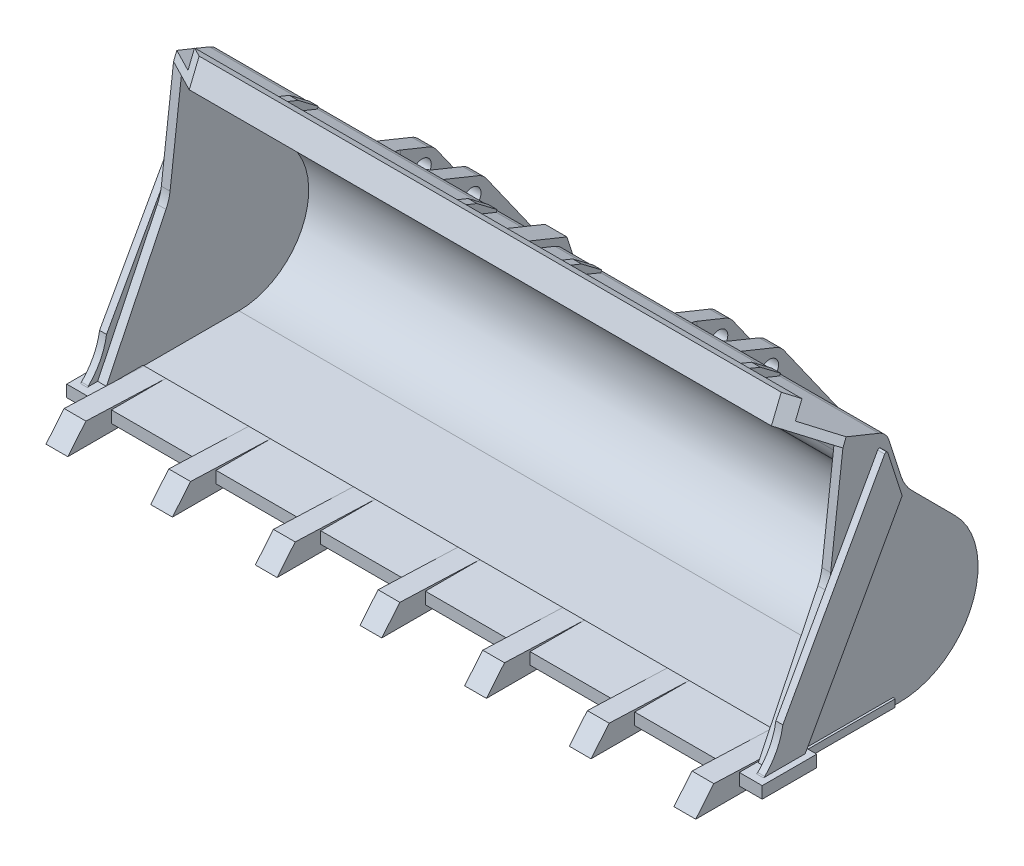
SolidWorks part; units mm, degrees
ref_plane "Front Plane" through (0, 0, 0) normal (0, 0, 1) x (1, 0, 0)
ref_plane "Top Plane" through (0, 0, 0) normal (0, 1, 0) x (1, 0, 0)
ref_plane "Right Plane" through (0, 0, 0) normal (1, 0, 0) x (0, 0, -1)
sketch "Sketch1" plane through (0, 0, 0) normal (1, 0, 0) x (0, 0, -1)
  line L0 (76.25, 0) -> (0, 0)
  line L1 (0, 0) -> (0, 5)
  line L2 (0, 5) -> (36.25, 80)
  line L3 (36.25, 80) -> (43.75, 142.5)
  line L4 (43.75, 142.5) -> (27.7663, 148.9871)
  line L5 (27.7663, 148.9871) -> (33.4072, 162.886)
  line L6 (33.4072, 162.886) -> (38.0402, 161.0057)
  line L7 (38.0402, 161.0057) -> (34.2795, 151.7398)
  line L8 (34.2795, 151.7398) -> (68.7006, 137.7697)
  line L9 (68.7006, 137.7697) -> (78.9617, 106.0197)
  line L10 (78.9617, 106.0197) -> (108.1198, 76.7697)
  arc A0 (108.1198, 76.7697) -> (76.25, 0) centre (76.25, 45) cw
  dimension "D15" = 45
  dimension "D1" = 5
  dimension "D2" = 80
  dimension "D3" = 36.25
  dimension "D4" = 142.5
  dimension "D5" = 43.75
  dimension "D6" = 76.25
  dimension "D7" = 17.25
  dimension "D8" = 10
  dimension "D9" = 5
  dimension "D10" = 5
  dimension "D11" = 130
  dimension "D12" = 153
  dimension "D13" = 31.75
  dimension "D14" = 29.25
extrude "Boss-Extrude1" add sketch "Sketch1" against normal blind 191.875
fillet "Fillet1" radius 25 1 edges at (-95.9375, 106.0197, -78.9617)
fillet "Fillet2" radius 10 1 edges at (-95.9375, 137.7697, -68.7006)
fillet "Fillet3" radius 25 1 edges at (-95.9375, 80, -36.25)
shell "Shell1" thickness 5 removed face at (-191.875, 99.0116, -50.2449) removed face at (-95.9375, 2.5, 0) removed face at (-95.9375, 40.6214, -17.217) removed face at (-95.9375, 80.1451, -35.7543) removed face at (-95.9375, 113.3217, -40.2486)
sketch "Sketch3" plane through (-191.875, 0, 0) normal (-1, 0, 0) x (0, 0, 1)
  line L0 (0, 5) -> (0, 0) construction
  line L1 (-21.25, 5.5) -> (10, 5.5)
  line L2 (-21.25, 5.5) -> (-21.25, -1.25)
  line L3 (-21.25, -1.25) -> (10, -1.25)
  line L4 (10, 5.5) -> (10, -1.25)
  line L5 (0, 0) -> (-76.25, 0) construction
  dimension "D1" = 31.25
  dimension "D2" = 6.75
  dimension "D3" = 10
  dimension "D4" = 1.25
extrude "Boss-Extrude3" add sketch "Sketch3" against normal blind 199.375
sketch "Sketch4" plane through (-191.875, 0, 0) normal (-1, 0, 0) x (0, 0, 1)
  line L1 (-21.25, 0) -> (-72.5, 0)
  line L2 (-21.25, 0) -> (-21.25, 4.25)
  line L3 (-21.25, 4.25) -> (-72.5, 4.25)
  line L4 (-72.5, 0) -> (-72.5, 4.25)
  dimension "D1" = 51.25
  dimension "D2" = 4.25
extrude "Boss-Extrude4" add sketch "Sketch4" against normal blind 193.125
sketch "Sketch5" plane through (0, 0, 0) normal (1, 0, 0) x (0, 0, -1)
  line L0 (-7, 4) -> (17.2963, 4)
  line L1 (17.2963, 4) -> (73.7585, 105.8605)
  line L2 (73.7585, 105.8605) -> (64.8101, 133.5489)
  line L3 (64.8101, 133.5489) -> (5.3334, 26.25)
  line L4 (77.1159, 111.7308) -> (70.1346, 133.3326) construction
  line L5 (-10, -1.25) -> (-10, 5.5) construction
  line L6 (-10, 5.5) -> (21.25, 5.5) construction
  line L7 (-7, 4) -> (5.3334, 26.25) construction
  arc A0 (5.3334, 26.25) -> (-7, 4) centre (-30.7557, 31.7113) cw
  point P12 (0, 0)
  point P13 (18.5775, 4)
  dimension "D5" = 36.5
  dimension "D1" = 5
  dimension "D2" = 61
  dimension "D3" = 3
  dimension "D4" = 1.5
  dimension "D6" = 22.25
  dimension "D7" = 21.25
extrude "Boss-Extrude5" add sketch "Sketch5" along normal blind 4
fillet "Fillet4" radius 1 3 edges at (2, 5.5, 5.3546) (2, 105.8605, -73.7585) (2, 133.5489, -64.8101)
sketch "Sketch6" plane through (0, 142.2251, -57.723) normal (0, 0.9266, -0.3761) x (1, 0, 0)
  line L0 (0, -13.0507) -> (0, -30.3007)
  line L1 (0, -30.3007) -> (-25, -30.3007)
  line L2 (-191.875, -30.3007) -> (0, -30.3007) construction
  line L3 (-25, -30.3007) -> (0, -13.0507)
  dimension "D1" = 25
extrude "Cut-Extrude1" cut sketch "Sketch6" against normal up to next and the other way through all
sketch "Sketch7" plane through (-191.875, 0, 0) normal (-1, 0, 0) x (0, 0, 1)
  line L0 (-77.1159, 111.7308) -> (-70.1346, 133.3326) construction
  line L1 (-64.3799, 139.5233) -> (-34.2795, 151.7398) construction
  line L2 (-77.1159, 111.7308) -> (-70.1346, 133.3326)
  line L3 (-64.3799, 139.5233) -> (-34.2795, 151.7398)
  line L4 (-45.848, 147.0446) -> (-47.2582, 150.5194)
  line L5 (-47.2582, 150.5194) -> (-71.1264, 140.8323)
  line L6 (-71.1264, 140.8323) -> (-79.3776, 115.3012)
  line L7 (-79.3776, 115.3012) -> (-76.285, 114.3018)
  arc A0 (-64.3799, 139.5233) -> (-70.1346, 133.3326) centre (-60.6192, 130.2574) ccw construction
  arc A1 (-64.3799, 139.5233) -> (-70.1346, 133.3326) centre (-60.6192, 130.2574) ccw
  point P7 (-76.2775, 114.3252)
  arc M25 (-64.3799, 139.5233) -> (-70.1346, 133.3326) centre (-60.6192, 130.2574) ccw
  line M26 (-70.1346, 133.3326) -> (-77.1159, 111.7308)
  dimension "D1" = 3.75
  dimension "D2" = 3.25
  dimension "D3" = 20
  dimension "D4" = 20
extrude "Boss-Extrude6" add sketch "Sketch7" against normal blind 6.25 contours L6 L7 L3 L4 L5 M26 M25 region at (-191.875, 115.2711, -77.6795)
sketch "Sketch8" plane through (0, 142.2251, -57.723) normal (0, 0.9266, -0.3761) x (1, 0, 0)
  line L0 (0, 7.1842) -> (-185.625, 7.1842) construction
  line L1 (-164.375, 7.1842) -> (-159.375, 7.1842)
  line L2 (-164.375, 7.1842) -> (-164.375, -25.3007)
  line L3 (-164.375, -25.3007) -> (-159.375, -25.3007)
  line L4 (-159.375, 7.1842) -> (-159.375, -25.3007)
  line L5 (-191.875, -25.3007) -> (-17.7536, -25.3007) construction
  line L6 (-191.875, -25.3007) -> (-17.7536, -25.3007) construction
  line L7 (-61.875, 7.1842) -> (-56.875, 7.1842)
  line L8 (-61.875, 7.1842) -> (-61.875, -25.3007)
  line L9 (-61.875, -25.3007) -> (-56.875, -25.3007)
  line L10 (-56.875, 7.1842) -> (-56.875, -25.3007)
  line L11 (-191.875, -12.8158) -> (-191.875, -25.3007) construction
  dimension "D1" = 102.5
  dimension "D2" = 27.5
  dimension "D3" = 5
  dimension "D4" = 5
extrude "Boss-Extrude7" add sketch "Sketch8" along normal blind 5
chamfer "Chamfer1" distance 3.75 angle 75 2 edges at (-59.375, 144.1563, -66.2602) (-161.875, 144.1563, -66.2602) first distance on face at (-59.375, 141.8398, -65.32) first distance on face at (-161.875, 141.8398, -65.32)
mirror "Mirror1" about plane through (-191.875, 45, -76.25) normal (-1, 0, 0) of bodies 108
ref_plane "Plane1" through (-191.875, 0, 0) normal (1, 0, 0) x (0, 0, -1)
sketch "Sketch10" plane through (-191.875, 0, 0) normal (1, 0, 0) x (0, 0, -1)
  line L0 (108.1198, 76.7697) -> (83.199, 101.769) construction
  line L1 (77.1159, 111.7308) -> (70.1346, 133.3326) construction
  line L2 (70.1346, 133.3326) -> (76.285, 114.3018) construction
  line L3 (108.1198, 76.7697) -> (83.199, 101.769)
  line L4 (77.1159, 111.7308) -> (70.1346, 133.3326)
  line L5 (70.1346, 133.3326) -> (76.285, 114.3018)
  line L6 (72.5, 0) -> (21.25, 0) construction
  line L7 (72.5, 0) -> (76.25, 0) construction
  line L8 (72.5, 0) -> (21.25, 0)
  line L9 (72.5, 0) -> (76.25, 0)
  line L10 (21.25, 0) -> (21.25, -0.625)
  line L11 (21.25, 5.5) -> (21.25, -1.25) construction
  line L12 (21.25, -0.625) -> (137.6551, -0.625)
  line L13 (145.0861, 7.8907) -> (138.2745, 57.7252)
  line L14 (133.9237, 68.7643) -> (97.3071, 120.597)
  line L15 (70.1346, 133.3326) -> (92.9002, 124.0931)
  line L17 (64.3799, 139.5233) -> (45.6303, 147.133) construction
  arc A0 (76.25, 0) -> (108.1198, 76.7697) centre (76.25, 45) ccw construction
  arc A1 (77.1159, 111.7308) -> (83.199, 101.769) centre (100.9045, 119.4189) ccw construction
  arc A2 (76.25, 0) -> (108.1198, 76.7697) centre (76.25, 45) ccw
  arc A3 (77.1159, 111.7308) -> (83.199, 101.769) centre (100.9045, 119.4189) ccw
  arc A4 (138.2745, 57.7252) -> (133.9237, 68.7643) centre (113.5048, 54.3397) ccw
  arc A5 (97.3071, 120.597) -> (92.9002, 124.0931) centre (89.1395, 114.8271) ccw
  arc A6 (137.6551, -0.625) -> (145.0861, 7.8907) centre (137.6551, 6.875) ccw
  point P16 (0, 0)
  point P17 (151.7996, -2.5244)
  point P18 (0, 0)
  point P19 (123.2809, 60.1814)
  point P20 (91.2029, 115.6584)
  point P21 (21.25, 51.5357)
  point P22 (196.068, -36.4809)
  point P23 (21.25, -6.8107)
  point P24 (21.25, -0.8791)
  point P25 (139.6483, 64.2748)
  point P26 (141.5232, 73.8215)
  point P27 (136.2982, 68.765)
  point P28 (129.4882, 109.2436)
  point P29 (134.0323, 83.6466)
  point P30 (95.616, 122.9908)
  point P31 (0, 0)
  point P32 (123.2809, 60.1814)
  point P34 (93.0536, 119.6324)
  point P36 (137.3188, 63.7585)
  point P39 (137.4475, 63.7762)
  point P42 (95.616, 122.9908)
  point P45 (146.25, -0.625)
  dimension "D6" = 25
  dimension "D7" = 10
  dimension "D8" = 7.5
  dimension "D1" = 27.5
  dimension "D2" = 125
  dimension "D3" = 0.625
  dimension "D4" = 65
  dimension "D5" = 72.5
extrude "Boss-Extrude8" add sketch "Sketch10" along normal mid plane 208.75 separate body contours L12 A6 L13 A4 L14 A5 L15 L4 A3 L3 A2 L9 L8 L10 region at (-191.875, 90.5576, -96.9517)
sketch "Sketch11" plane through (0, 0, 0) normal (0, 1, 0) x (1, 0, 0)
  line L0 (-191.875, 53.6511) -> (-191.875, -43.2917) construction
  line L1 (-191.875, -56.7172) -> (-191.875, 56.7172) construction
  line L2 (0, 0) -> (-360.078, 0) construction
  line L3 (-267.125, 203.7051) -> (-286.625, 203.7051)
  line L4 (-258.125, 0) -> (-125.625, 0)
  line L5 (-258.125, 0) -> (-258.125, 203.7051)
  line L6 (-258.125, 203.7051) -> (-125.625, 203.7051)
  line L7 (-125.625, 0) -> (-125.625, 203.7051)
  line L9 (-116.625, 76.8769) -> (-116.625, 203.7051)
  line L10 (-116.625, 203.7051) -> (-97.125, 203.7051)
  line L11 (-97.125, 76.8769) -> (-97.125, 203.7051)
  line L12 (-286.625, 76.8769) -> (-286.625, 203.7051)
  line L13 (-378.75, 65.3769) -> (-5, 65.3769) construction
  line L14 (-267.125, 76.8769) -> (-267.125, 203.7051)
  line L15 (-87.5, 145.1551) -> (-296.25, 145.1551) construction
  arc A0 (-97.125, 76.8769) -> (-116.625, 76.8769) centre (-106.875, 76.8769) cw
  arc A1 (-267.125, 76.8769) -> (-286.625, 76.8769) centre (-276.875, 76.8769) cw
  point P20 (0, 0)
  point P22 (-107.375, 112.6761)
  point P23 (-116.625, 104.5787)
  point P24 (-116.625, 112.5219)
  point P25 (-98.125, 112.5219)
  point P26 (-116.625, 104.5787)
  point P27 (-98.125, 104.5787)
  point P28 (-116.625, 104.5787)
  point P29 (-98.125, 104.5787)
  point P30 (-98.125, 104.5787)
  point P31 (-107.375, 99.34)
  point P32 (-107.375, 112.6479)
  point P33 (0, 0)
  point P34 (-98.125, 111.1855)
  point P37 (-106.875, 67.1269)
  point P38 (0, 0)
  point P41 (0, 0)
  point P42 (-191.875, 0)
  dimension "D1" = 189.5
  dimension "D2" = 150.5
  dimension "D3" = 132.5
  dimension "D4" = 1.75
  dimension "D5" = 58.55
extrude "Cut-Extrude2" cut sketch "Sketch11" against normal through all and the other way through all
sketch "Sketch12" plane through (-191.875, 0, 0) normal (1, 0, 0) x (0, 0, -1)
  circle A0 centre (137.6551, 6.875) radius 5.25
  circle A1 centre (89.1395, 114.8271) radius 5.25
  dimension "D1" = 10.5
  dimension "D2" = 10.5
extrude "Cut-Extrude3" cut sketch "Sketch12" against normal through all both and the other way through all
combine bodies "Combine1" operation type add bodies to combine 109 114 113
sketch "Sketch13" plane through (-191.875, 0, 0) normal (1, 0, 0) x (0, 0, -1)
  line L0 (21.25, 5.5) -> (18.75, -1.25)
  line L1 (21.25, -1.25) -> (-10, -1.25) construction
  line L2 (18.75, -1.25) -> (18.75, -5.25)
  line L3 (18.75, -5.25) -> (-35, -5.25)
  line L4 (-35, -5.25) -> (-24.6167, 7.25)
  line L5 (-24.6167, 7.25) -> (21.25, 5.5)
  line L6 (21.25, 5.5) -> (21.25, -1.25) construction
  dimension "D1" = 4
  dimension "D2" = 2.5
  dimension "D3" = 25
  dimension "D4" = 16.25
  dimension "D5" = 12.5
extrude "Boss-Extrude9" add sketch "Sketch13" along normal mid plane 12.5
pattern_linear "LPattern1" count 4 spacing 60 along (-1, 0, 0) count 4 spacing 60 along (1, 0, 0) of "Boss-Extrude9"
